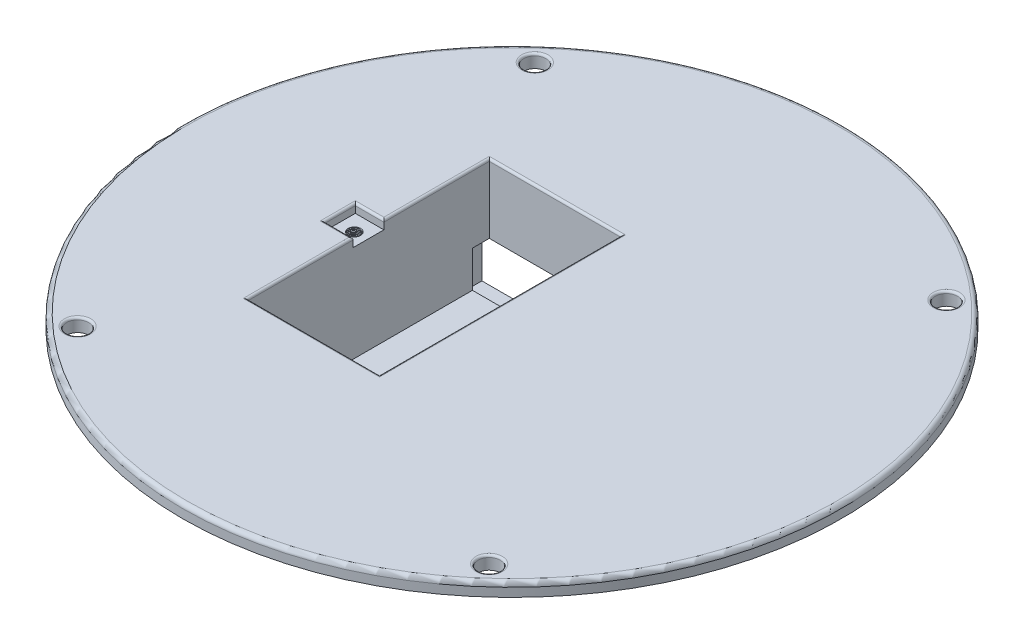
SolidWorks part; units mm, degrees
ref_plane "Front Plane" through (0, 0, 0) normal (0, 0, 1) x (1, 0, 0)
ref_plane "Top Plane" through (0, 0, 0) normal (0, 1, 0) x (1, 0, 0)
ref_plane "Right Plane" through (0, 0, 0) normal (1, 0, 0) x (0, 0, -1)
sketch "Sketch2" plane through (0, 0, 0) normal (0, 1, 0) x (1, 0, 0)
  circle A0 centre (0, 0) radius 75
extrude "Boss-Extrude1" add sketch "Sketch2" along normal blind 3
fillet "Fillet1" radius 1 1 edges at (0, 3, 75)
sketch "Sketch3" plane through (0, 0, 0) normal (0, -1, 0) x (1, 0, 0)
  line L1 (0, -28) -> (-36, -28)
  line L2 (0, -28) -> (0, 28)
  line L3 (0, 28) -> (-36, 28)
  line L4 (-36, -28) -> (-36, 28)
  dimension "D1" = 36
  dimension "D2" = 56
  dimension "D3" = 28
  dimension "D4" = 36
extrude "Boss-Extrude2" add sketch "Sketch3" along normal blind 24
sketch "Sketch4" plane through (0, 3, 0) normal (0, 1, 0) x (1, 0, 0)
  line L1 (-3, -27.1612) -> (-33, -27.1612)
  line L2 (-3, -27.1612) -> (-3, 27.8388)
  line L3 (-3, 27.8388) -> (-33, 27.8388)
  line L4 (-33, -27.1612) -> (-33, 27.8388)
  dimension "D1" = 30
  dimension "D2" = 55
  dimension "D3" = 28
  dimension "D4" = 33
extrude "Cut-Extrude2" cut sketch "Sketch4" against normal blind 24
sketch "Sketch5" plane through (0, 0, -28) normal (0, 0, -1) x (-1, 0, 0)
  line L1 (1.2128, -12.683) -> (34.8469, -12.683)
  line L2 (1.2128, -12.683) -> (1.2128, -22.0617)
  line L3 (1.2128, -22.0617) -> (34.8469, -22.0617)
  line L4 (34.8469, -12.683) -> (34.8469, -22.0617)
extrude "Cut-Extrude3" cut sketch "Sketch5" against normal blind 4
sketch "Sketch6" plane through (0, 3, 0) normal (0, 1, 0) x (1, 0, 0)
  line L1 (49.5076, -55) -> (-49.5076, -55) construction
  line L2 (49.5076, -55) -> (49.5076, 55) construction
  line L3 (49.5076, 55) -> (-49.5076, 55) construction
  line L4 (-49.5076, -55) -> (-49.5076, 55) construction
  line L5 (49.5076, -55) -> (-49.5076, 55) construction
  line L6 (49.5076, 55) -> (-49.5076, -55) construction
  circle A0 centre (0, 0) radius 74 construction
  circle A1 centre (-46.8315, 52.027) radius 2.5
  circle A3 centre (-46.8315, -52.027) radius 2.5
  circle A6 centre (46.8315, -52.027) radius 2.5
  circle A7 centre (46.8315, 52.027) radius 2.5
  point P0 (0, 0)
  dimension "D2" = 70
  dimension "D1" = 110
  dimension "D3" = 70
  dimension "D4" = 70
  dimension "D5" = 70
extrude "Cut-Extrude4" cut sketch "Sketch6" against normal blind 10
sketch "Sketch7" plane through (0, 3, 0) normal (0, 1, 0) x (1, 0, 0)
  line L2 (-36, 3) -> (-33, 3)
  line L3 (-33, 27.8388) -> (-33, -27.1612) construction
  line L4 (-33, 3) -> (-33, -3)
  line L5 (-33, -3) -> (-36, -3)
  circle A1 centre (-36, 0) radius 3
  arc A2 (-36, -3) -> (-36, 3) centre (-36, 0) cw
  line M7 (-33, -27.1612) -> (-33, 27.8388)
  dimension "D1" = 33
extrude "Boss-Extrude3" add sketch "Sketch7" against normal blind 20 contours A1 L4 L2 | A1 | A1 L5 M7 region at (-33.6701, 3, -2.3299) region at (-36, 3, 0) region at (-33.6701, 3, 2.3299)
sketch "Sketch8" plane through (0, 3, 0) normal (0, 1, 0) x (1, 0, 0)
  circle A0 centre (-36, 0) radius 1.5
  dimension "D1" = 33
extrude "Cut-Extrude5" cut sketch "Sketch8" against normal blind 10
thread "Thread1" pitch 0.3175 method extrude profile "Thread Profile1" start angle 0, offset 0, length 5, pitch 0.3175, diameter 3
ref_plane "Plane1" through (-37.5, 3, 0) normal (0, 0, 1) x (-1, 0, 0)
sketch "Thread Profile1" plane through (-37.5, 3, 0) normal (0, 0, 1) x (-1, 0, 0)
  line L0 (0, 0) -> (0, 0.3175) construction
  line L11 (0, 0) -> (0, 0.2778)
  line L12 (0, 0.2778) -> (-0.1719, 0.1786)
  line L13 (-0.1719, 0.1786) -> (-0.1719, 0.0992)
  line L15 (-0.1719, 0.0992) -> (0, 0)
  line L17 (-0.1719, 0.1389) -> (0, 0.1389) construction
  point P2 (0, 0)
  dimension "Pitch" = 0.3175
  dimension "Profile_Angle" = 60
  dimension "Profile_Land" = 0.0794
  dimension "Profile_Height" = 0.1719
sketch "Sketch12" plane through (0, 3, 0) normal (0, 1, 0) x (1, 0, 0)
  line L0 (-33, 27.8388) -> (-33, -27.1612) construction
  line L1 (-39.5, 3.8388) -> (-32.5, 3.8388)
  line L2 (-39.5, 3.8388) -> (-39.5, -3.1612)
  line L3 (-39.5, -3.1612) -> (-32.5, -3.1612)
  line L4 (-32.5, 3.8388) -> (-32.5, -3.1612)
  point P6 (-32.5, 0.3388)
  point P9 (-37.1611, -11.7622)
  dimension "D1" = 7
  dimension "D2" = 7
  dimension "D3" = 0.5
  dimension "D4" = 27.5
extrude "Cut-Extrude8" cut sketch "Sketch12" against normal blind 2 body kept at (75, 2, 0)
fillet "Fillet2" radius 0.5 12 edges at (-46.8315, 3, -49.527) (46.8315, 3, 54.527) (-46.8315, 3, 54.527) (46.8315, 3, -49.527) (-39.5, 3, -0.3388) (-36.25, 3, 3.1612) (-33, 3, 15.1612) (-18, 3, 27.1612) (-3, 3, -0.3388) (-18, 3, -27.8388) (-33, 3, -15.8388) (-36.25, 3, -3.8388)
